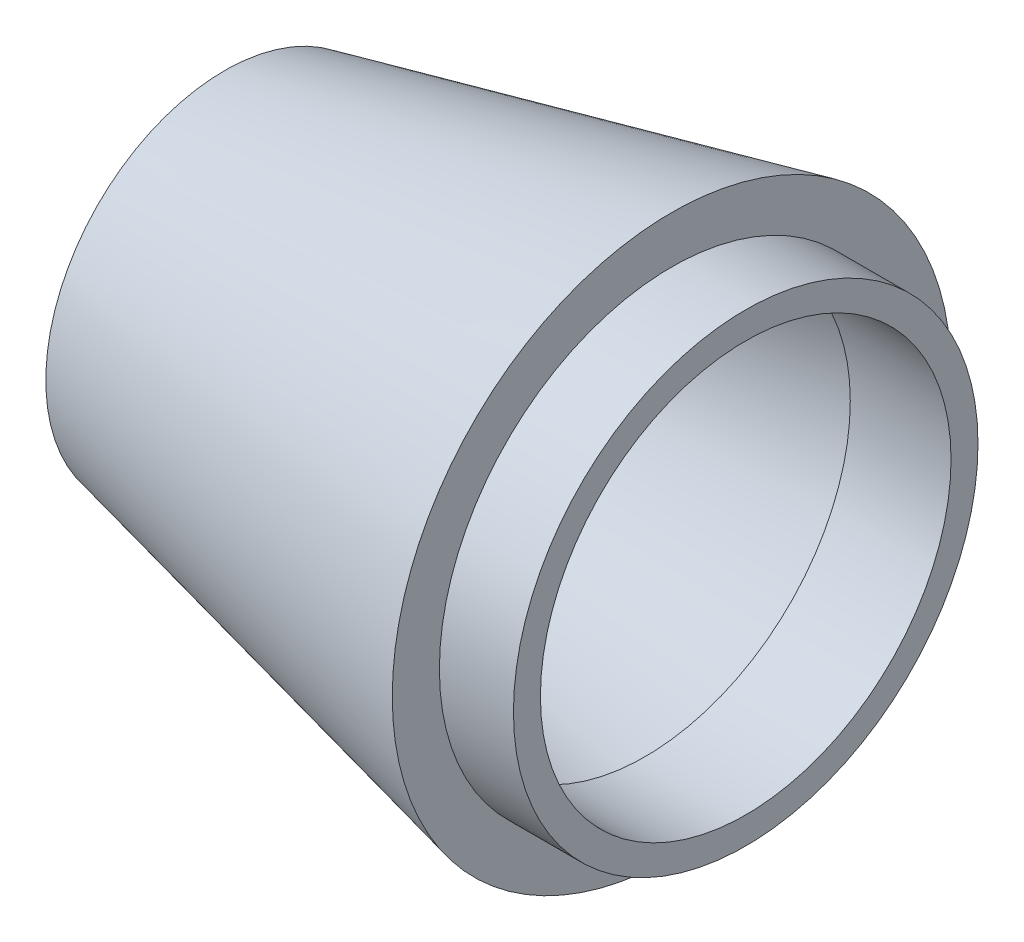
SolidWorks part; units mm, degrees
ref_plane "Front Plane" through (0, 0, 0) normal (0, 0, 1) x (1, 0, 0)
ref_plane "Top Plane" through (0, 0, 0) normal (0, 1, 0) x (1, 0, 0)
ref_plane "Right Plane" through (0, 0, 0) normal (1, 0, 0) x (0, 0, -1)
sketch "Sketch1" plane through (0, 0, 0) normal (0, 0, 1) x (1, 0, 0)
  line L0 (-12.065, 10.16) -> (-12.065, 7.62)
  line L1 (44.7264, 0) -> (-69.8413, 0) construction
  line L2 (13.335, 15.875) -> (13.335, 13.1977)
  line L3 (-12.065, 0) -> (14.2126, 0) construction
  line L4 (-0.8483, 12.6838) -> (-0.8483, 0)
  line L5 (13.335, 15.875) -> (-12.065, 10.16)
  line L6 (-12.065, 7.62) -> (13.335, 13.1977)
  line L7 (-0.8483, 0) -> (0.635, 0)
  line L8 (0.635, 0) -> (0.635, 13.0175)
  line L9 (0.635, 13.0175) -> (-0.8483, 12.6838)
  line L11 (13.335, 11.6659) -> (11.8182, 11.6659)
  line L12 (11.8182, 11.6659) -> (11.8182, 12.8646)
  line L13 (11.8182, 12.8646) -> (13.335, 13.1977)
  line L14 (13.335, 13.1977) -> (17.5428, 13.1977)
  line L15 (17.5428, 11.6659) -> (13.335, 11.6659)
  line L16 (17.5428, 13.1977) -> (17.5428, 11.6659)
  point P10 (0, 0)
  dimension "D1" = 25.4
revolve "Revolve4" add sketch "Sketch1" angle 360 about L1 region at (-6.4346, 10.1416, 0) region at (-0.1027, 5.1234, 0) region at (7.0125, 13.1309, 0)
